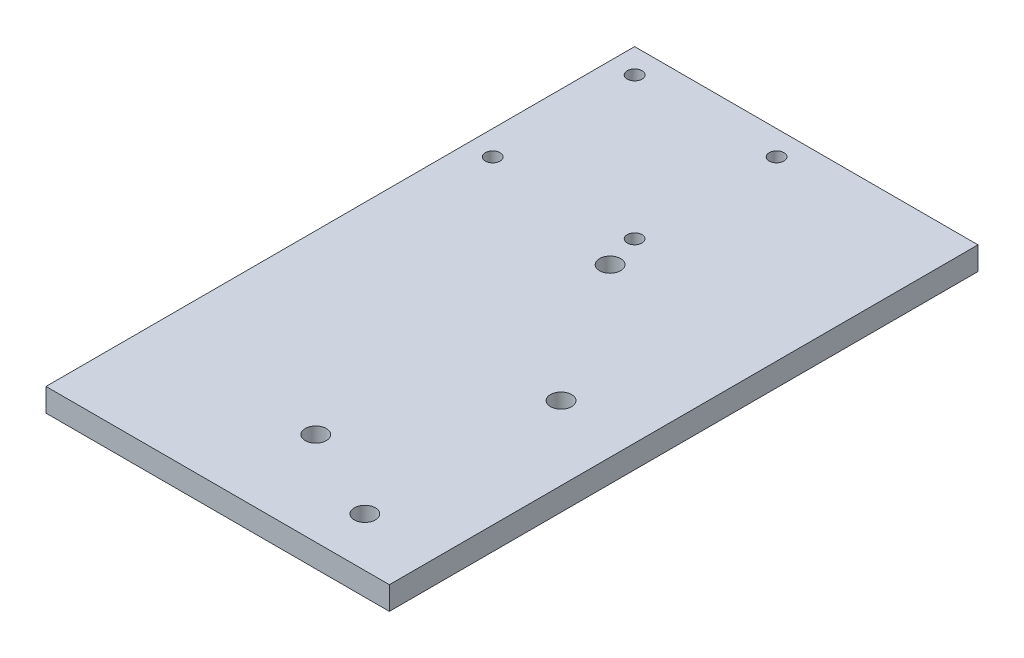
SolidWorks part; units mm, degrees
ref_plane "Front Plane" through (0, 0, 0) normal (0, 0, 1) x (1, 0, 0)
ref_plane "Top Plane" through (0, 0, 0) normal (0, 1, 0) x (1, 0, 0)
ref_plane "Right Plane" through (0, 0, 0) normal (1, 0, 0) x (0, 0, -1)
sketch "Sketch2" plane through (0, 0, 0) normal (0, 1, 0) x (1, 0, 0)
  line L2 (0, 0) -> (0, 152.4)
  line L4 (88.9, 0) -> (88.9, 152.4)
  line L10 (-1000, 76.2) -> (49000, 76.2) construction
  line L13 (0, 152.4) -> (88.9, 152.4)
  line L14 (0, 0) -> (88.9, 0)
  point P11 (0, 76.2)
  dimension "D1" = 152.4
  dimension "D2" = 88.9
extrude "Boss-Extrude1" add sketch "Sketch2" along normal blind 5.9944 contours L4 L13 L2 L14
sketch "Sketch4" plane through (0, 5.9944, 0) normal (0, 1, 0) x (1, 0, 0)
  line L0 (0, 0) -> (0, 152.4) construction
  line L1 (0, 0) -> (88.9, 0) construction
  line L2 (45.72, 100.33) -> (45.72, 24.13) construction
  circle A0 centre (45.72, 100.33) radius 2.7305
  circle A1 centre (45.72, 24.13) radius 2.7305
  point P4 (45.72, 62.23)
  point P6 (0, 0)
  point P8 (45.72, 62.2922)
  point P9 (45.72, 55.267)
  point P10 (45.72, 59.9504)
  dimension "D3" = 5.461
  dimension "D4" = 5.461
  dimension "D1" = 76.2
  dimension "D2" = 45.72
  dimension "D5" = 62.23
extrude "Cut-Extrude2" cut sketch "Sketch4" against normal through all both
sketch "Sketch5" plane through (0, 5.9944, 0) normal (0, 1, 0) x (1, 0, 0)
  line L0 (88.9, 0) -> (88.9, 152.4) construction
  line L5 (0, 0) -> (88.9, 0) construction
  circle A0 centre (69.85, 63.5) radius 2.7305
  circle A1 centre (69.85, 12.7) radius 2.7305
  dimension "D1" = 5.461
  dimension "D2" = 5.461
  dimension "D3" = 50.8
  dimension "D6" = 19.05
  dimension "D7" = 12.7
extrude "Cut-Extrude3" cut sketch "Sketch5" against normal through all both and the other way through all
sketch "Sketch6" plane through (0, 5.9944, 0) normal (0, 1, 0) x (1, 0, 0)
  line L0 (0, 152.4) -> (88.9, 152.4) construction
  line L1 (43.1038, 146.05) -> (6.35, 146.05) construction
  line L2 (43.1038, 146.05) -> (43.1038, 109.2962) construction
  line L3 (43.1038, 109.2962) -> (6.35, 109.2962) construction
  line L4 (6.35, 146.05) -> (6.35, 109.2962) construction
  line L5 (0, 0) -> (0, 152.4) construction
  circle A0 centre (43.1038, 109.2962) radius 1.905
  circle A1 centre (6.35, 109.2962) radius 1.905
  circle A2 centre (6.35, 146.05) radius 1.905
  circle A3 centre (43.1038, 146.05) radius 1.905
  point P8 (43.6725, 108.9519)
  dimension "D3" = 3.81
  dimension "D4" = 3.81
  dimension "D5" = 3.81
  dimension "D6" = 3.81
  dimension "D7" = 6.35
  dimension "D1" = 36.7538
  dimension "D2" = 36.7538
  dimension "D8" = 6.35
extrude "Cut-Extrude4" cut sketch "Sketch6" against normal through all both and the other way through all
equation "\"threaded_insert_hole\"=0.1472"
equation "\"th\"=1.25249"
